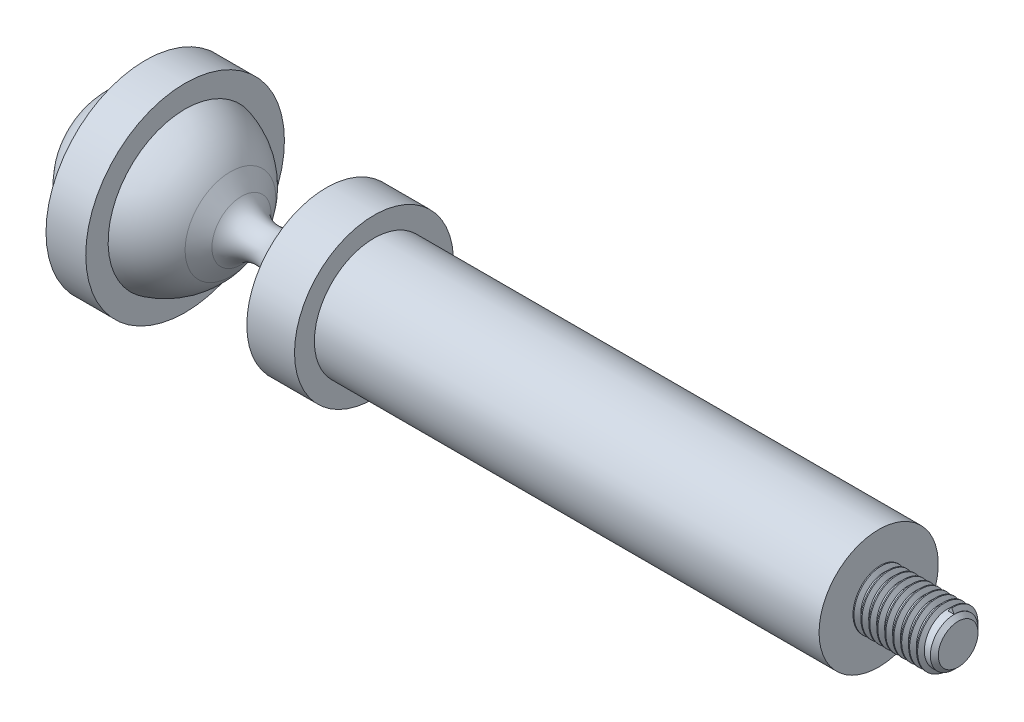
SolidWorks part; units mm, degrees
ref_plane "Front Plane" through (0, 0, 0) normal (0, 0, 1) x (1, 0, 0)
ref_plane "Top Plane" through (0, 0, 0) normal (0, 1, 0) x (1, 0, 0)
ref_plane "Right Plane" through (0, 0, 0) normal (1, 0, 0) x (0, 0, -1)
sketch "Sketch1" plane through (0, 0, 0) normal (0, 0, 1) x (1, 0, 0)
  line L0 (-51.938, 0) -> (57.9443, 0) construction
  line L1 (-31.8229, 10.04) -> (-31.8229, 12.5) construction
  line L2 (-29.3229, 9.6825) -> (-29.3229, 12.5)
  line L3 (-34.3229, 9.6825) -> (-34.3229, 12.5)
  line L4 (-34.3229, 0) -> (-34.3229, 12.5) construction
  line L5 (-31.8229, 0) -> (-31.8229, 12.5) construction
  line L6 (-29.3229, 0) -> (-29.3229, 12.5) construction
  line L7 (-34.3229, 12.5) -> (-29.3229, 12.5)
  line L8 (-22.2269, 3.7162) -> (-23.6131, 5.7094)
  line L9 (-15.5933, 3.8138) -> (-11.5557, 10)
  line L10 (-11.5557, 10) -> (-5.5557, 10)
  line L11 (-5.5557, 7.5) -> (57.9443, 7.5)
  line L12 (-51.938, 7.5) -> (57.9443, 7.5) construction
  line L13 (-5.5557, 10) -> (-5.5557, 7.5)
  line L14 (57.9443, 3) -> (67.9443, 3)
  line L15 (57.9443, 7.5) -> (57.9443, 3)
  line L16 (67.9443, 3) -> (67.9443, 0)
  line L17 (67.9443, 0) -> (-41.8229, 0)
  arc A0 (-34.3229, 9.6825) -> (-41.8229, 0) centre (-31.8229, 0) ccw
  arc A1 (-23.6131, 5.7094) -> (-29.3229, 9.6825) centre (-31.8229, 0) ccw
  arc A2 (-22.2269, 3.7162) -> (-15.5933, 3.8138) centre (-18.9429, 6) ccw
  point P25 (0, 0)
  dimension "D1" = 7.5
  dimension "D5" = 8
  dimension "D8" = 6
  dimension "D2" = 2.5
  dimension "D4" = 12.5
  dimension "D6" = 10
  dimension "D7" = 6
  dimension "D10" = 63.5
  dimension "D11" = 3
  dimension "D12" = 10
  dimension "D13" = 57.9443
  dimension "D14" = 15.5933
  dimension "D15" = 22.2269
  dimension "D3" = 2.5
  dimension "D9" = 7.5
revolve "Revolve1" add sketch "Sketch1" angle 360 about L0
chamfer "Chamfer1" distance 0.5 angle 45 1 edges at (67.9443, 0, 3)
thread "Thread2" pitch 1 method extrude profile "Thread Profile3" start angle 90, offset 0, length 0, pitch 1, diameter 6
ref_plane "Plane3" through (67.4443, 3, 0) normal (0, 0, 1) x (0, 1, 0)
sketch "Thread Profile3" plane through (67.4443, 3, 0) normal (0, 0, 1) x (0, 1, 0)
  line L0 (0, 0) -> (0, 1) construction
  line L1 (0, 0) -> (0.5413, 0.3125)
  line L2 (0.5413, 0.3125) -> (0.5413, 0.4375)
  line L3 (0.5413, 0.4375) -> (0, 0.75)
  line L4 (0.5413, 0.375) -> (0, 0.375) construction
  line L11 (0, 0) -> (0, 0.75)
  point P2 (0, 0)
  dimension "Pitch" = 1
  dimension "Profile_Angle" = 60
  dimension "Profile_Land" = 0.125
  dimension "Profile_Height" = 0.5413
